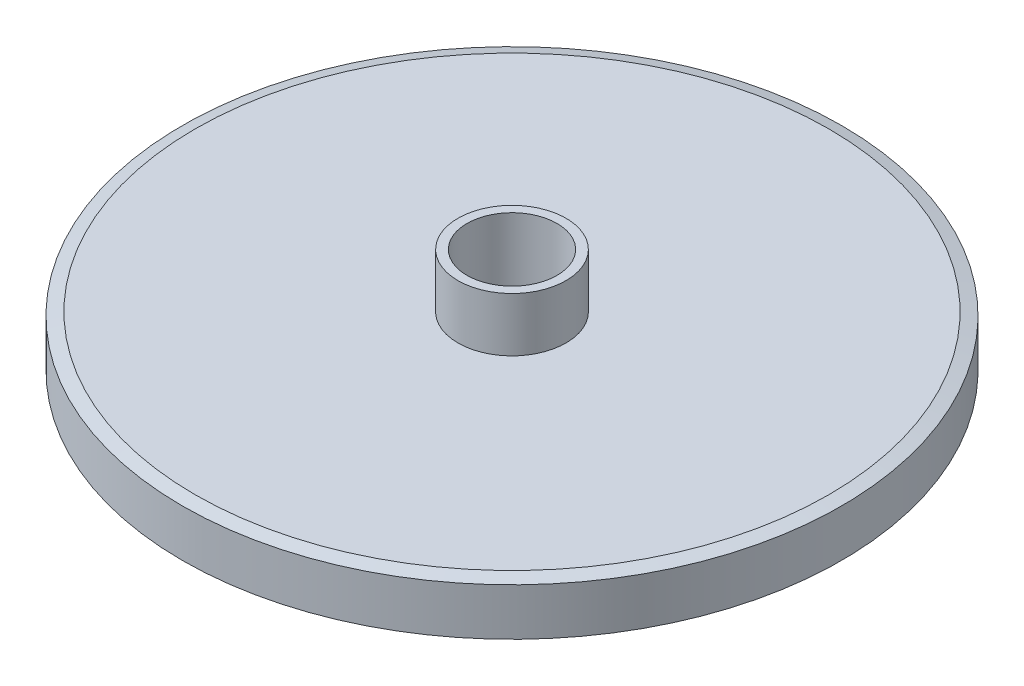
SolidWorks part; units mm, degrees
material "Сталь ШХ15 ГОСТ 801-78"
ref_plane "Plane1" through (0, 0, 0) normal (0, 0, 1) x (1, 0, 0)
ref_plane "Plane2" through (0, 0, 0) normal (0, 1, 0) x (1, 0, 0)
ref_plane "Plane3" through (0, 0, 0) normal (1, 0, 0) x (0, 0, -1)
sketch "Эскиз1" plane through (0, 0, 0) normal (0, 0, 1) x (1, 0, 0)
  line L0 (0, 0) -> (18.3, 0)
  line L1 (18.3, 0) -> (18.3, 3)
  line L2 (18.3, 3) -> (3, 3)
  line L3 (3, 3) -> (3, 6)
  line L4 (3, 6) -> (0, 6)
  line L5 (0, 6) -> (0, 0)
  dimension "D1" = 3
  dimension "30" = 18.3
  dimension "D3" = 3
  dimension "D4" = 3
ref_axis "Ось1" through (0, 6, 0) along (0, -1, 0)
revolve "Повернуть2" add sketch "Эскиз1" angle 360 about axis through (0, 6, 0) along (0, -1, 0)
chamfer "Фаска1" distance 0.705 angle 15 1 edges at (0, 3, 18.3) first distance on face at (0, 3, 3)
sketch "Эскиз2" plane through (0, 0, 0) normal (0, -1, 0) x (-1, 0, 0)
  circle A0 centre (0, 0) radius 2.5
sketch "Эскиз3" plane through (0, 0, 0) normal (1, 0, 0) x (0, 0, -1)
  circle A0 centre (0, 7.4791) radius 1
extrude "Вырез-Вытянуть3" cut sketch "Эскиз2" against normal through all both
chamfer "Фаска2" distance 0.705 angle 15 1 edges at (0, 0, 18.3) first distance on face at (0, 0, -2.5)
